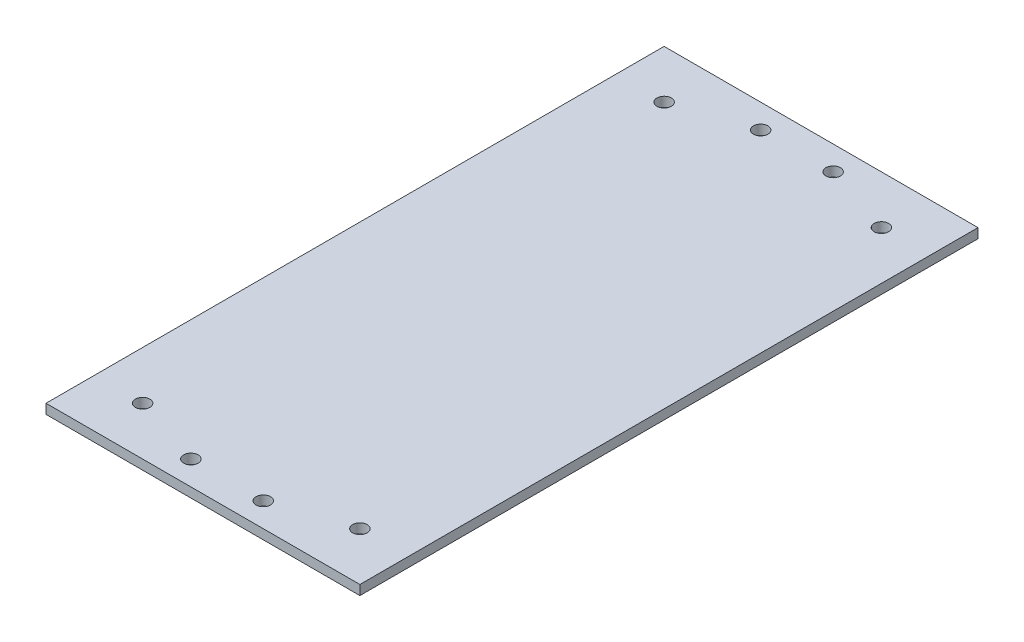
SolidWorks part; units mm, degrees
ref_plane "Спереди" through (0, 0, 0) normal (0, 0, 1) x (1, 0, 0)
ref_plane "Сверху" through (0, 0, 0) normal (0, 1, 0) x (1, 0, 0)
ref_plane "Справа" through (0, 0, 0) normal (1, 0, 0) x (0, 0, -1)
sketch "Эскиз1" plane through (0, 0, 0) normal (0, 1, 0) x (1, 0, 0)
  line L0 (-41.8585, 53.6415) -> (-41.8585, -74.3585) construction
  line L1 (-74.3585, 53.6415) -> (-9.3585, 53.6415)
  line L2 (-74.3585, 53.6415) -> (-74.3585, -74.3585)
  line L3 (-74.3585, -74.3585) -> (-9.3585, -74.3585)
  line L4 (-9.3585, 53.6415) -> (-9.3585, -74.3585)
  line L5 (-74.3585, -10.3585) -> (-9.3585, -10.3585) construction
  circle A0 centre (-64.3585, 43.6415) radius 1.5
  circle A1 centre (-19.3585, 43.6415) radius 1.5
  circle A2 centre (-19.3585, -64.3585) radius 1.5
  circle A3 centre (-64.3585, -64.3585) radius 1.5
  point P0 (0, 0)
  point P12 (-41.8585, -10.3585)
  dimension "D1" = 10
  dimension "D2" = 10
  dimension "D3" = 128
  dimension "D4" = 65
extrude "Бобышка-Вытянуть1" add sketch "Эскиз1" along normal blind 2
sketch "Эскиз2" plane through (0, 2, 0) normal (0, 1, 0) x (1, 0, 0)
  line L0 (-41.8585, 53.6415) -> (-41.8585, -74.3585) construction
  line L1 (-9.3585, 53.6415) -> (-74.3585, 53.6415) construction
  line L2 (-74.3585, -74.3585) -> (-9.3585, -74.3585) construction
  line L3 (-74.3585, -10.3585) -> (-9.3585, -10.3585) construction
  line L4 (-74.3585, 53.6415) -> (-74.3585, -74.3585) construction
  line L5 (-9.3585, -74.3585) -> (-9.3585, 53.6415) construction
  circle A0 centre (-49.3585, 48.6415) radius 1.5
  circle A1 centre (-34.3585, 48.6415) radius 1.5
  circle A2 centre (-34.3585, -69.3585) radius 1.5
  circle A3 centre (-49.3585, -69.3585) radius 1.5
  dimension "D1" = 3
  dimension "D2" = 5
  dimension "D3" = 7.5
extrude "Вырез-Вытянуть1" cut sketch "Эскиз2" against normal through all
